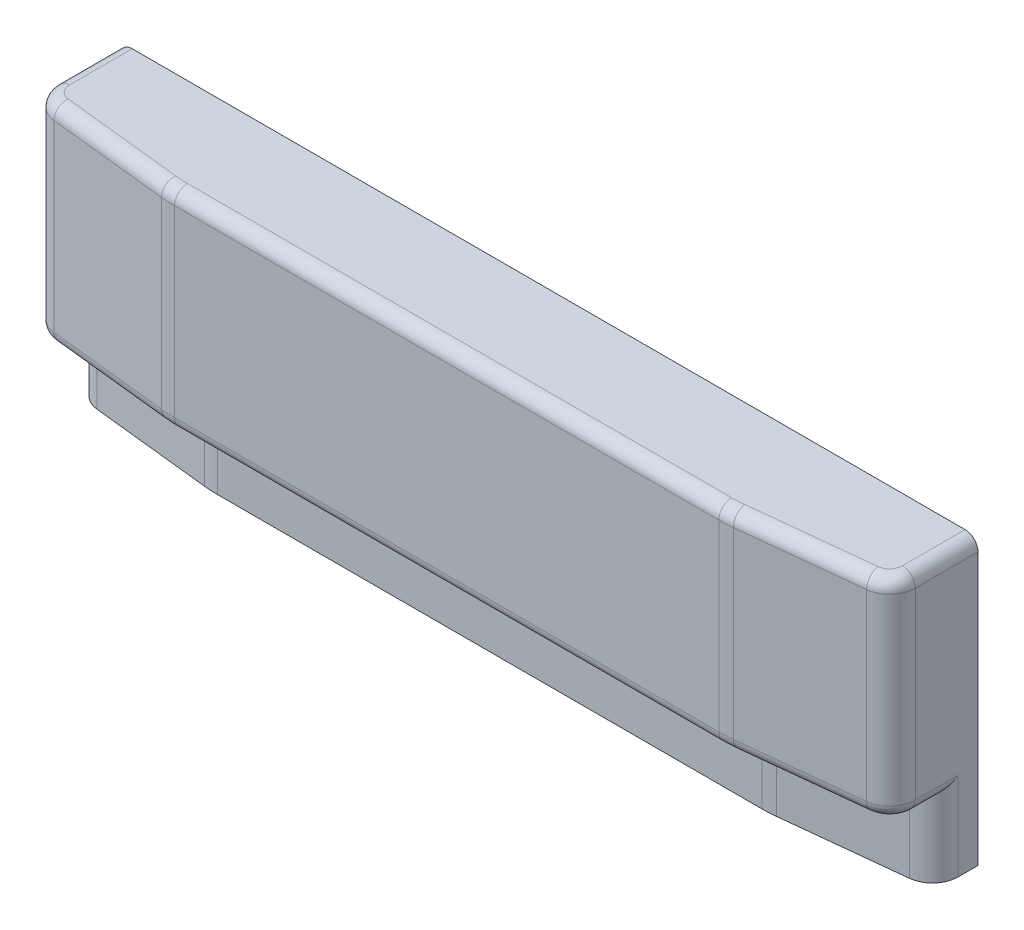
SolidWorks part; units mm, degrees
other "Camera1"
ref_plane "Front Plane" through (0, 0, 0) normal (0, 0, 1) x (1, 0, 0)
ref_plane "Top Plane" through (0, 0, 0) normal (0, 1, 0) x (1, 0, 0)
ref_plane "Right Plane" through (0, 0, 0) normal (1, 0, 0) x (0, 0, -1)
sketch "Sketch7" plane through (0, 0, 0) normal (0, 1, 0) x (1, 0, 0)
  line L0 (0, 0) -> (508, 0)
  line L1 (508, 0) -> (508, -50.8)
  line L2 (508, -50.8) -> (419.1, -60.325)
  line L3 (419.1, -60.325) -> (88.9, -60.325)
  line L4 (88.9, -60.325) -> (0, -50.8)
  line L5 (0, -50.8) -> (0, 0)
  dimension "D1" = 508
  dimension "D2" = 50.8
  dimension "D3" = 88.9
  dimension "D4" = 88.9
  dimension "D5" = 60.325
extrude "Boss-Extrude1" add sketch "Sketch7" along normal blind 168.275
ref_plane "Wall Plane" through (0, 0, 0) normal (0, 0, 1) x (1, 0, 0)
ref_plane "Floor Plane" through (0, 0, 0) normal (0, 1, 0) x (1, 0, 0)
sketch "Sketch10" plane through (0, 0, 0) normal (0, -1, 0) x (1, 0, 0)
  line L0 (0, 50.8) -> (0, 25.4)
  line L1 (0, 0) -> (0, 50.8) construction
  line L2 (0, 25.4) -> (88.9, 34.925)
  line L3 (88.9, 34.925) -> (419.1, 34.925)
  line L4 (419.1, 34.925) -> (508, 25.4)
  line L5 (508, 50.8) -> (508, 0) construction
  line L6 (508, 25.4) -> (508, 50.8)
  line L7 (508, 50.8) -> (419.1, 60.325)
  line L8 (419.1, 60.325) -> (88.9, 60.325)
  line L9 (88.9, 60.325) -> (0, 50.8)
  dimension "D1" = 25.4
extrude "Cut-Extrude1" cut sketch "Sketch10" against normal blind 44.45
fillet "Fillet1" radius 15.24 4 edges at (508, 22.225, 25.4) (508, 106.3625, 50.8) (0, 22.225, 25.4) (0, 106.3625, 50.8)
fillet "Fillet2" radius 76.2 4 edges at (419.1, 22.225, 34.925) (419.1, 106.3625, 60.325) (88.9, 22.225, 34.925) (88.9, 106.3625, 60.325)
fillet "Fillet3" radius 7.62 9 edges at (0, 168.275, 18.5528) (3.9042, 168.275, 47.2918) (49.2346, 168.275, 56.0751) (88.9058, 168.275, 60.2165) (508, 168.275, 18.5528) (504.0958, 168.275, 47.2918) (458.7654, 168.275, 56.0751) (419.0942, 168.275, 60.2165) (254, 168.275, 60.325)
fillet "Fillet4" radius 7.62 9 edges at (508, 44.45, 24.4056) (504.0958, 44.45, 47.2918) (458.7654, 44.45, 56.0751) (419.0942, 44.45, 60.2165) (0, 44.45, 24.4056) (3.9042, 44.45, 47.2918) (49.2346, 44.45, 56.0751) (88.9058, 44.45, 60.2165) (254, 44.45, 60.325)
